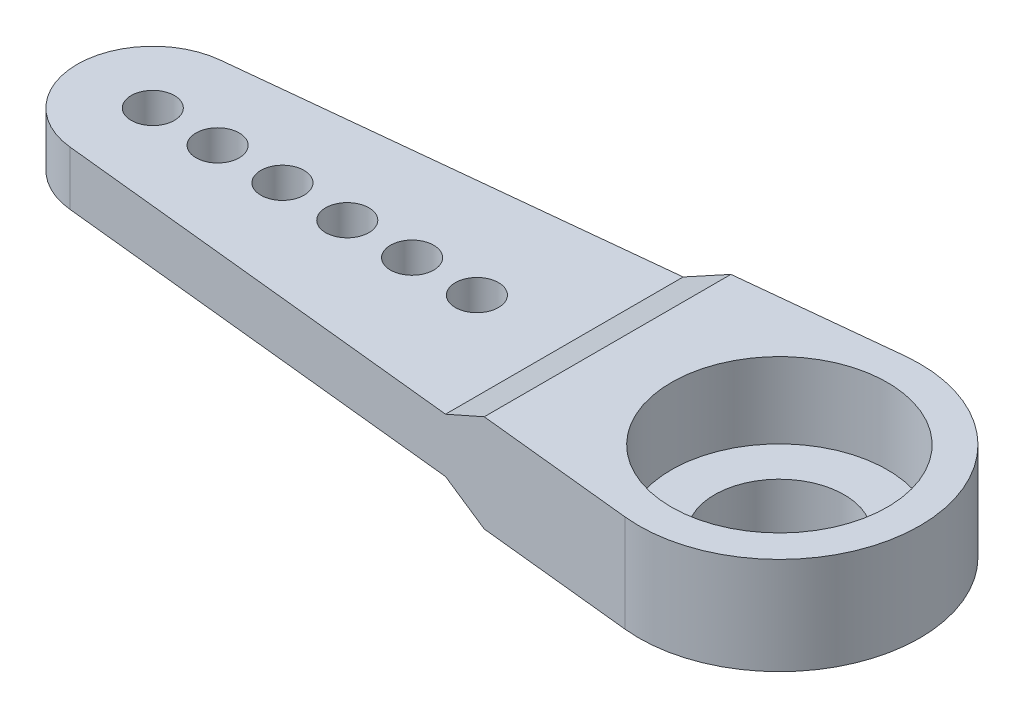
SolidWorks part; units mm, degrees
ref_plane "Спереди" through (0, 0, 0) normal (0, 0, 1) x (1, 0, 0)
ref_plane "Сверху" through (0, 0, 0) normal (0, 1, 0) x (1, 0, 0)
ref_plane "Справа" through (0, 0, 0) normal (1, 0, 0) x (0, 0, -1)
other "Configuration Table"
sketch "Эскиз1" plane through (0, 0, 0) normal (0, 1, 0) x (1, 0, 0)
  line L0 (-29.3621, -3.4812) -> (-0.6724, -6.4651)
  line L1 (-0.6724, 6.4651) -> (-29.3621, 3.4812)
  line L2 (0, 0) -> (0, 27.9909) construction
  line L3 (0, 0) -> (-44.1421, 0) construction
  line L4 (-32.5, 0) -> (-32.5, 8.563) construction
  line L5 (6.5, 0) -> (6.5, 8.563) construction
  line L6 (-9.9519, -5.5) -> (-9.9519, 5.5)
  circle A0 centre (0, 0) radius 3
  circle A1 centre (0, 0) radius 3.5
  circle A2 centre (0, 0) radius 5
  arc A3 (-0.6724, -6.4651) -> (-0.6724, 6.4651) centre (0, 0) ccw
  arc A4 (-29.3621, 3.4812) -> (-29.3621, -3.4812) centre (-29, 0) ccw
  circle A5 centre (-14, 0) radius 1
  circle A6 centre (-17, 0) radius 1
  circle A7 centre (-20, 0) radius 1
  circle A8 centre (-23, 0) radius 1
  circle A9 centre (-26, 0) radius 1
  circle A10 centre (-29, 0) radius 1
  dimension "D1" = 6
  dimension "D2" = 7
  dimension "D3" = 10
  dimension "D4" = 13
  dimension "D5" = 7
  dimension "D6" = 2
  dimension "D9" = 39
  dimension "D7" = 14
  dimension "D10" = 11
  dimension "D8" = 6
extrude "Бобышка-Вытянуть1" add sketch "Эскиз1" along normal blind 2.5 contours L1 A4 L0 L6 A10 A9 A8 A7 A6 A5 | L0 A3 L1 L6 A2 region at (-32.2491, 0, 0) region at (-9.7422, 0, 0)
extrude "Бобышка-Вытянуть2" add sketch "Эскиз1<3>" along normal blind 1 from surface contours L0 A3 L1 L6 A2 region at (-9.7422, 0, 0) starting at face at (-29, 2.5, 1)
sketch "Эскиз1<3>" plane through (0, 0, 0) normal (0, 1, 0) x (1, 0, 0) same geometry as "Эскиз1"
extrude "Бобышка-Вытянуть3" add sketch "Эскиз1<4>" against normal blind 1 contours L0 A3 L1 L6 A2 region at (-9.7422, 0, 0)
sketch "Эскиз1<4>" plane through (0, 0, 0) normal (0, 1, 0) x (1, 0, 0) same geometry as "Эскиз1"
extrude "Бобышка-Вытянуть4" add sketch "Эскиз1<5>" against normal blind 2.5 contours A2 A1 | A1 A0 region at (-3.401, 0, 0) region at (-4.8586, 0, 0)
sketch "Эскиз1<5>" plane through (0, 0, 0) normal (0, 1, 0) x (1, 0, 0) same geometry as "Эскиз1"
chamfer "Фаска1" distance 1 distance2 2 2 edges at (-9.9519, 3.5, 0) (-9.9519, -1, 0) first distance on face at (-9.9519, 3, 0) first distance on face at (-9.9519, -0.5, 0)
chamfer "Фаска2" distance 1 angle 45 1 edges at (0, -2.5, 5)
